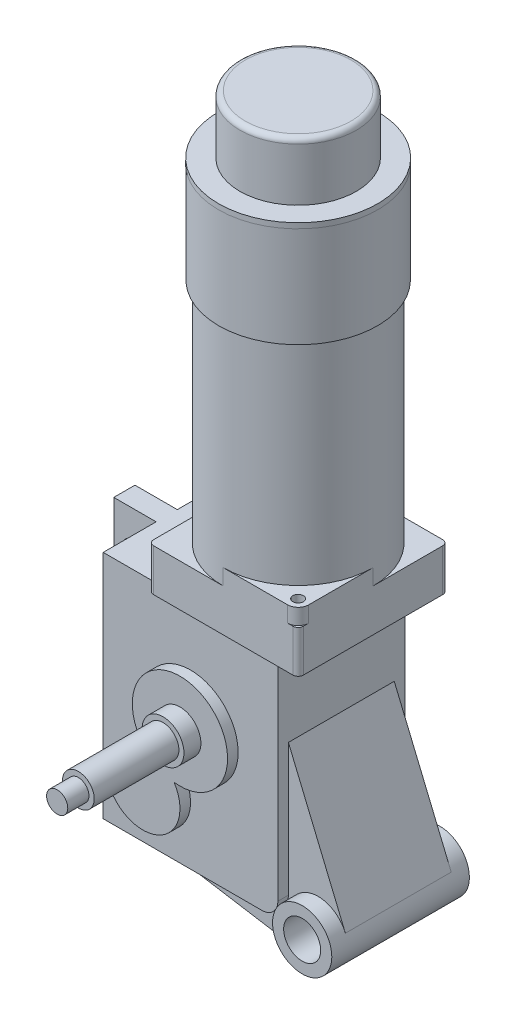
SolidWorks part; units mm, degrees
ref_plane "Front" through (0, 0, 0) normal (0, 0, 1) x (1, 0, 0)
ref_plane "Top" through (0, 0, 0) normal (0, 1, 0) x (1, 0, 0)
ref_plane "Right" through (0, 0, 0) normal (1, 0, 0) x (0, 0, -1)
sketch "Sketch2" plane through (0, 0, 0) normal (0, 1, 0) x (1, 0, 0)
  circle A0 centre (0, 0) radius 47.625
  dimension "D1" = 95.25
extrude "Extrude1" add sketch "Sketch2" against normal blind 63.5
sketch "Sketch3" plane through (0, 0, 0) normal (0, 1, 0) x (1, 0, 0)
  circle A0 centre (0, 0) radius 44.958
  dimension "D1" = 89.916
extrude "Extrude2" add sketch "Sketch3" against normal blind 190.5
sketch "Sketch4" plane through (0, 0, 0) normal (0, 1, 0) x (1, 0, 0)
  circle A0 centre (0, 0) radius 34.925
  dimension "D1" = 69.85
extrude "Extrude3" add sketch "Sketch4" along normal blind 34.925
fillet "Fillet1" radius 3.175 1 edges at (0, 34.925, 34.925)
sketch "Sketch5" plane through (0, -190.5, 0) normal (0, -1, 0) x (1, 0, 0)
  line L0 (0, 44.958) -> (38.608, 44.958)
  line L1 (44.958, 38.608) -> (44.958, 0)
  circle A1 centre (0, 0) radius 44.958 construction
  arc A2 (0, 44.958) -> (44.958, 0) centre (0, 0) ccw
  arc A3 (38.608, 44.958) -> (44.958, 38.608) centre (38.608, 38.608) cw
  circle A4 centre (38.608, 38.608) radius 3.175
  dimension "D1" = 6.35
  dimension "D2" = 6.35
extrude "Extrude4" add sketch "Sketch5" along normal blind 9.525
sketch "Sketch6" plane through (0, -200.025, 0) normal (0, -1, 0) x (1, 0, 0)
  line L0 (38.608, 44.958) -> (0, 44.958) construction
  line L1 (-41.783, -44.958) -> (41.783, -44.958)
  line L2 (-44.958, -41.783) -> (-44.958, 41.783)
  line L3 (-41.783, 44.958) -> (41.783, 44.958)
  line L4 (44.958, -41.783) -> (44.958, 41.783)
  line L5 (44.958, 0) -> (44.958, 38.608) construction
  arc A0 (0, 44.958) -> (44.958, 0) centre (0, 0) ccw construction
  arc A1 (-44.958, 41.783) -> (-41.783, 44.958) centre (-41.783, 41.783) cw
  arc A2 (41.783, 44.958) -> (44.958, 41.783) centre (41.783, 41.783) cw
  arc A3 (41.783, -44.958) -> (44.958, -41.783) centre (41.783, -41.783) ccw
  arc A4 (-41.783, -44.958) -> (-44.958, -41.783) centre (-41.783, -41.783) cw
  dimension "D1" = 3.175
extrude "Extrude5" add sketch "Sketch6" along normal blind 25.4
sketch "Sketch7" plane through (0, -225.425, 0) normal (0, -1, 0) x (1, 0, 0)
  line L1 (25.908, -38.1) -> (-78.867, -38.1)
  line L2 (25.908, -38.1) -> (25.908, 38.1)
  line L3 (25.908, 38.1) -> (-78.867, 38.1)
  line L4 (-78.867, -38.1) -> (-78.867, 38.1)
  line L6 (44.958, -41.783) -> (44.958, 41.783) construction
  line L10 (44.958, 0) -> (25.908, 0) construction
  point P4 (25.908, 0)
  point P5 (44.958, 0)
  dimension "D1" = 19.05
  dimension "D2" = 104.775
  dimension "D3" = 76.2
extrude "Extrude6" add sketch "Sketch7" along normal blind 138.43
sketch "Sketch8" plane through (0, 0, 38.1) normal (0, 0, 1) x (1, 0, 0)
  line L0 (-44.958, -225.425) -> (-78.867, -225.425) construction
  line L1 (-26.4795, -363.855) -> (-26.4795, -225.425) construction
  line L2 (25.908, -363.855) -> (-78.867, -363.855) construction
  line L3 (25.908, -225.425) -> (-44.958, -225.425) construction
  circle A0 centre (-26.4795, -288.925) radius 23.8125 construction
  arc A1 (-48.597, -307.0178) -> (-29.9697, -317.2861) centre (-48.7045, -329.2425) ccw
  arc A2 (-29.9697, -317.2861) -> (-48.597, -307.0178) centre (-26.4795, -288.925) ccw
  dimension "D1" = 47.625
  dimension "D3" = 44.45
  dimension "D4" = 57.15
  dimension "D2" = 63.5
extrude "Extrude7" add sketch "Sketch8" along normal blind 6.35
mirror "Mirror1" about plane through (0, 0, 0) normal (0, 0, 1) of "Extrude7"
sketch "Sketch9" plane through (0, 0, 38.1) normal (0, 0, 1) x (1, 0, 0)
  line L0 (60.1003, -357.0165) -> (25.908, -274.955)
  line L1 (25.908, -363.855) -> (25.908, -225.425) construction
  line L2 (40.8103, -381.4006) -> (-66.167, -363.855)
  line L3 (25.908, -363.855) -> (-78.867, -363.855) construction
  line L4 (25.908, -274.955) -> (25.908, -363.855)
  line L5 (25.908, -363.855) -> (-66.167, -363.855)
  arc A0 (40.8103, -381.4006) -> (60.1003, -357.0165) centre (43.688, -363.855) ccw
  circle A1 centre (43.688, -363.855) radius 11.1125
  dimension "D1" = 22.225
  dimension "D2" = 35.56
  dimension "D3" = 12.7
  dimension "D4" = 88.9
extrude "Extrude8" add sketch "Sketch9" against normal offset from surface (63.5 mm away) 6.35 from offset 6.35 up to face at (-36.0592, -306.3032, -38.1) offset against normal yes
fillet "Fillet2" radius 9.525 2 edges at (25.908, -363.855, 34.925) (25.908, -363.855, -34.925)
sketch "Sketch10" plane through (0, 0, 38.1) normal (0, 0, 1) x (1, 0, 0)
  circle A0 centre (43.688, -363.855) radius 17.78
  circle A1 centre (43.688, -363.855) radius 11.1125 construction
  circle A2 centre (43.688, -363.855) radius 11.1125
  arc A3 (40.8103, -381.4006) -> (60.1003, -357.0165) centre (43.688, -363.855) ccw construction
extrude "Extrude9" add sketch "Sketch10" along normal blind 3.175 and the other way up to next
mirror "Mirror2" about plane through (0, 0, 0) normal (0, 0, 1) of "Extrude9"
sketch "Sketch11" plane through (0, -225.425, 0) normal (0, 1, 0) x (1, 0, 0)
  line L0 (-78.867, -38.1) -> (-78.867, 38.1) construction
  line L1 (-78.867, -6.35) -> (-104.267, -6.35)
  line L2 (-78.867, -6.35) -> (-78.867, 6.35)
  line L3 (-78.867, 6.35) -> (-104.267, 6.35)
  line L4 (-104.267, -6.35) -> (-104.267, 6.35)
  point P6 (-78.867, 0)
  dimension "D1" = 12.7
  dimension "D2" = 25.4
extrude "Attachment rail" add sketch "Sketch11" against normal up to surface (138.43 mm away) up to face at (-28.067, -363.855, 0)
sketch "Sketch16" plane through (0, 0, 0) normal (0, 0, 1) x (1, 0, 0)
  line L0 (-93.6307, -247.1738) -> (-93.6307, -348.7738) construction
  line L1 (-78.867, -363.855) -> (-78.867, -225.425) construction
  circle A0 centre (-93.6307, -247.1738) radius 5.1594
  circle A1 centre (-93.6307, -327.2282) radius 5.1594
  circle A2 centre (-93.6307, -348.7738) radius 5.1594
  circle A3 centre (43.688, -363.855) radius 11.1125 construction
  dimension "D1" = 163.9251
  dimension "D2" = 11.2268
  dimension "D3" = 91.2813
  dimension "D4" = 121.8726
  dimension "D5" = 10.3187
  dimension "D8" = 22.225
  dimension "D9" = 80.0545
  dimension "D10" = 21.5455
  dimension "D11" = 101.6
  dimension "D13" = 15.0812
  dimension "D12" = 137.3187
extrude "Attachment holes" cut sketch "Sketch16" against normal through all and the other way through all
sketch "Sketch12" plane through (0, 0, 44.45) normal (0, 0, 1) x (1, 0, 0)
  circle A0 centre (-26.4795, -288.925) radius 12.573
  dimension "D1" = 25.146
extrude "Extrude11" add sketch "Sketch12" along normal blind 10.16
sketch "Sketch13" plane through (0, 0, 54.61) normal (0, 0, 1) x (1, 0, 0)
  circle A0 centre (-26.4795, -288.925) radius 9.525
  dimension "D1" = 19.05
extrude "Extrude12" add sketch "Sketch13" along normal blind 50.8
sketch "Sketch14" plane through (0, 0, 105.41) normal (0, 0, 1) x (1, 0, 0)
  circle A0 centre (-26.4795, -288.925) radius 6.35
  dimension "D1" = 12.7
extrude "Extrude13" add sketch "Sketch14" along normal blind 12.7
sketch "Sketch15" plane through (0, 0, 0) normal (0, 1, 0) x (1, 0, 0)
  circle A0 centre (0, 0) radius 47.752
  dimension "D1" = 95.504
extrude "Extrude15" add sketch "Sketch15" against normal blind 3.175
ref_axis "Wheel Rotation Axis" through (-26.4795, -288.925, 197.0299) along (0, 0, -1)
